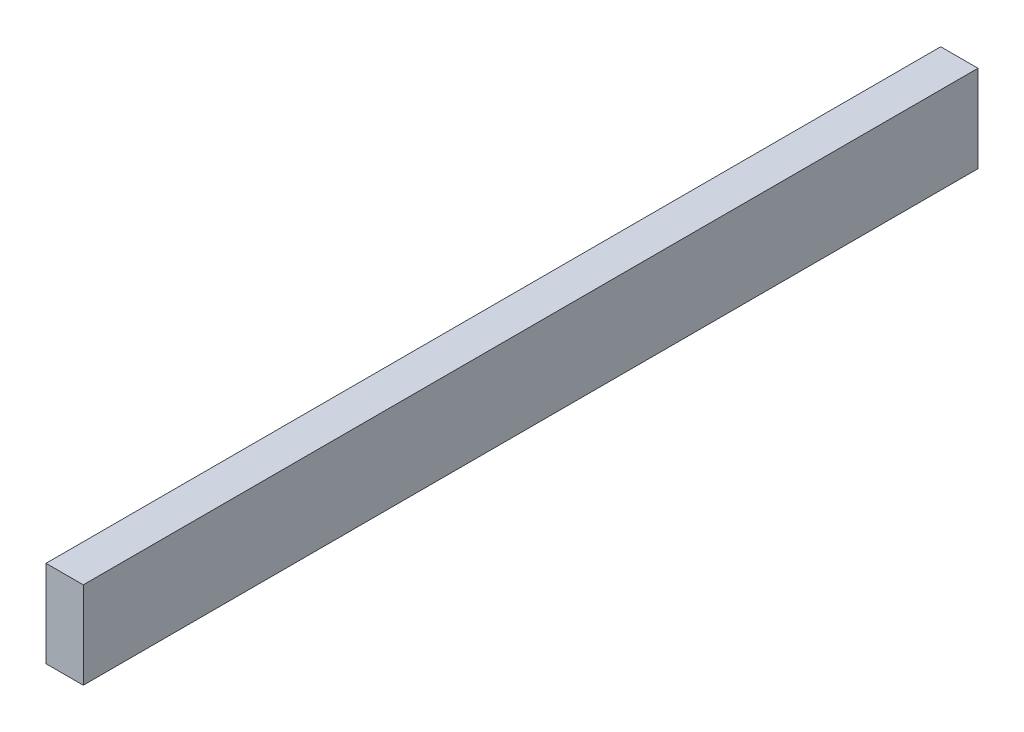
SolidWorks part; units mm, degrees
ref_plane "Front Plane" through (0, 0, 0) normal (0, 0, 1) x (1, 0, 0)
ref_plane "Top Plane" through (0, 0, 0) normal (0, 1, 0) x (1, 0, 0)
ref_plane "Right Plane" through (0, 0, 0) normal (1, 0, 0) x (0, 0, -1)
sketch "Sketch1" plane through (0, 0, 0) normal (0, 0, 1) x (1, 0, 0)
  line L1 (63.5, 1149.35) -> (25.4, 1149.35)
  line L2 (63.5, 1149.35) -> (63.5, 1060.45)
  line L3 (63.5, 1060.45) -> (25.4, 1060.45)
  line L4 (25.4, 1149.35) -> (25.4, 1060.45)
  dimension "D2" = 38.1
  dimension "D3" = 88.9
extrude "Boss-Extrude1" add sketch "Sketch1" along normal blind 914.4
